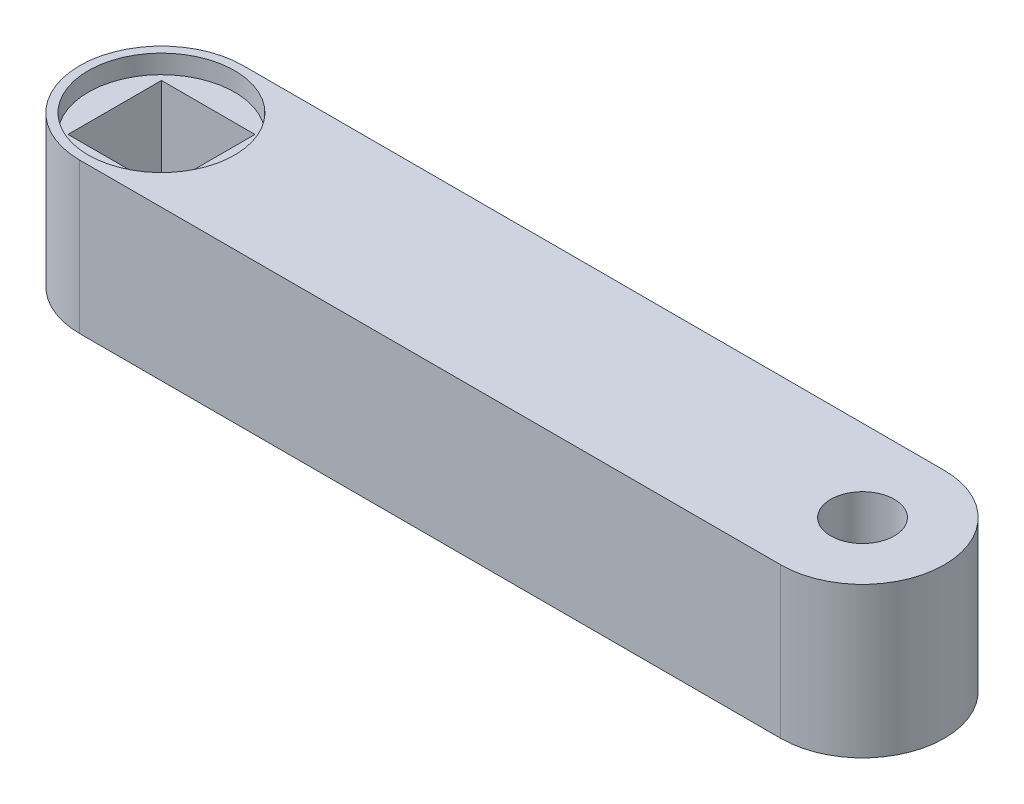
SolidWorks part; units mm, degrees
ref_plane "Front Plane" through (0, 0, 0) normal (0, 0, 1) x (1, 0, 0)
ref_plane "Top Plane" through (0, 0, 0) normal (0, 1, 0) x (1, 0, 0)
ref_plane "Right Plane" through (0, 0, 0) normal (1, 0, 0) x (0, 0, -1)
sketch "Sketch1" plane through (0, 0, 0) normal (0, 1, 0) x (1, 0, 0)
  line L0 (0, 0) -> (47.625, 0) construction
  line L1 (0, 5.5563) -> (47.625, 5.5563)
  line L2 (0, -5.5563) -> (47.625, -5.5563)
  arc A1 (0, 5.5563) -> (0, -5.5563) centre (0, 0) ccw
  arc A2 (47.625, -5.5563) -> (47.625, 5.5563) centre (47.625, 0) ccw
  point P3 (23.8125, 0)
  dimension "D1" = 11.1125
  dimension "D2" = 47.625
extrude "Boss-Extrude1" add sketch "Sketch1" along normal blind 10.2108
sketch "Sketch2" plane through (0, 10.2108, 0) normal (0, 1, 0) x (1, 0, 0)
  line L1 (-3.175, 3.175) -> (3.175, 3.175)
  line L2 (-3.175, 3.175) -> (-3.175, -3.175)
  line L3 (-3.175, -3.175) -> (3.175, -3.175)
  line L4 (3.175, 3.175) -> (3.175, -3.175)
  line L5 (-3.175, 3.175) -> (3.175, -3.175) construction
  line L6 (-3.175, -3.175) -> (3.175, 3.175) construction
  circle A1 centre (47.625, 0) radius 2.159
  point P0 (0, 0)
  dimension "D2" = 6.35
  dimension "D3" = 4.318
  dimension "D1" = 6.35
  dimension "D4" = 47.625
extrude "Cut-Extrude1" cut sketch "Sketch2" against normal through all
sketch "Sketch3" plane through (0, 10.2108, 0) normal (0, 1, 0) x (1, 0, 0)
  circle A0 centre (0, 0) radius 4.9721
  dimension "D1" = 9.9441
extrude "Cut-Extrude2" cut sketch "Sketch3" against normal blind 1.27
ref_plane "Plane1" through (0, 5.1054, 0) normal (0, 1, 0) x (1, 0, 0)
mirror "Mirror1" about plane through (0, 5.1054, 0) normal (0, 1, 0) of "Cut-Extrude2"
